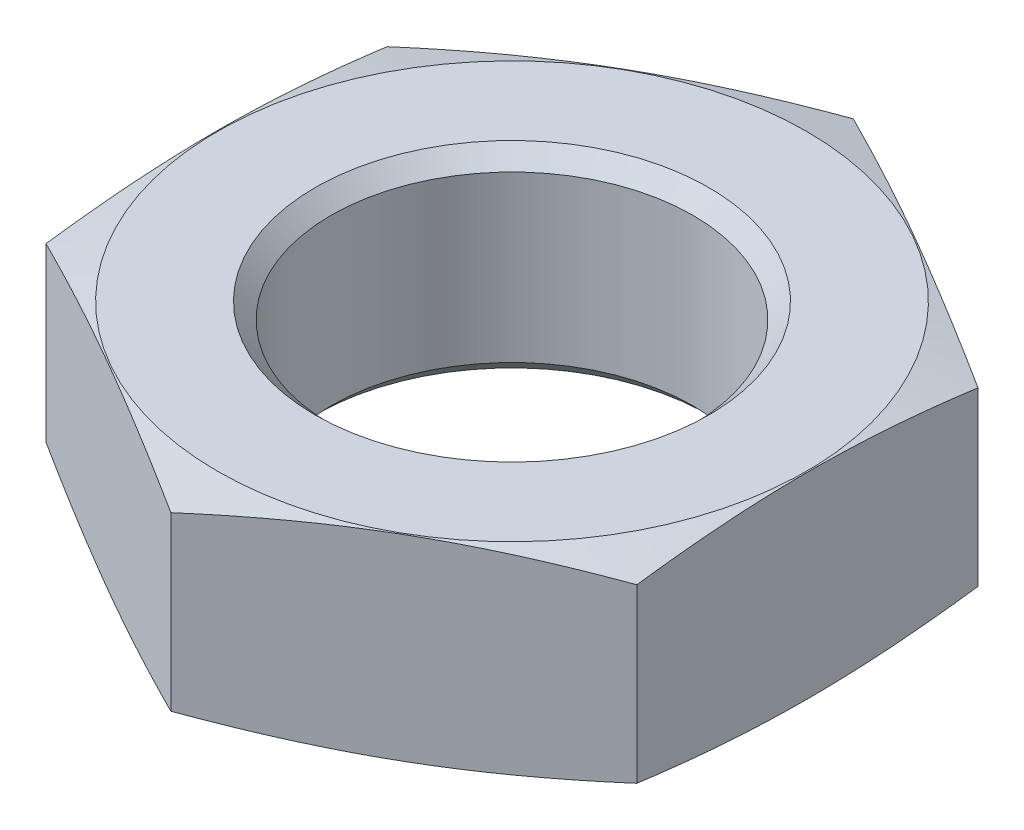
SolidWorks part; units mm, degrees
ref_plane "Front Plane" through (0, 0, 0) normal (0, 0, 1) x (1, 0, 0)
ref_plane "Top Plane" through (0, 0, 0) normal (0, 1, 0) x (1, 0, 0)
ref_plane "Right Plane" through (0, 0, 0) normal (1, 0, 0) x (0, 0, -1)
sketch "Sketch1" plane through (0, 0, 0) normal (0, 0, 1) x (1, 0, 0)
  line L0 (0, 0) -> (14.95, 0)
  line L1 (14.95, 0) -> (33.6103, -5)
  line L2 (33.6103, -5) -> (14.95, -10)
  line L3 (14.95, -10) -> (0, -10)
  line L4 (0, -10) -> (0, 0)
  line L5 (0, -10) -> (0, 0) construction
revolve "Revolve1" add sketch "Sketch1" angle 360 about L5
sketch "Sketch2" plane through (0, 0, 0) normal (0, 1, 0) x (1, 0, 0)
  line L0 (-60, 60) -> (-60, -60)
  line L1 (-60, -60) -> (60, -60)
  line L2 (60, -60) -> (60, 60)
  line L3 (60, 60) -> (-60, 60)
  line L4 (-15, -8.6603) -> (0, -17.3205)
  line L5 (0, -17.3205) -> (15, -8.6603)
  line L6 (15, -8.6603) -> (15, 8.6603)
  line L7 (15, 8.6603) -> (0, 17.3205)
  line L8 (0, 17.3205) -> (-15, 8.6603)
  line L9 (-15, 8.6603) -> (-15, -8.6603)
extrude "Cut-Extrude1" cut sketch "Sketch2" along normal blind 11 and the other way blind 11
sketch "Sketch3" plane through (0, 0, 0) normal (0, 0, 1) x (1, 0, 0)
  line L0 (0, 0) -> (10, 0)
  line L1 (10, 0) -> (9.188, -0.812)
  line L2 (9.188, -0.812) -> (9.188, -9.188)
  line L3 (9.188, -9.188) -> (10, -10)
  line L4 (10, -10) -> (0, -10)
  line L5 (0, -10) -> (0, 0)
  line L6 (0, -10) -> (0, 0) construction
revolve "Cut-Revolve1" cut sketch "Sketch3" angle 360 about L6 reverse direction yes
cosmetic thread "Cosmetic Thread1" parameters "D1"=10, "D2"=20
ref_plane "Plane1" through (0, -5, 0) normal (0, 1, 0) x (1, 0, 0)
ref_plane "2CYL XY" through (0, -5, 0) normal (0, 1, 0) x (1, 0, 0)
ref_plane "2CYL XZ" through (0, 0, 0) normal (0, 0, 1) x (1, 0, 0)
ref_plane "2CYL YZ" through (0, 0, 0) normal (1, 0, 0) x (0, 0, -1)
ref_axis "2CYL X" through (-80.9, -5, 0) along (1, 0, 0)
ref_axis "2CYL Y" through (0, -5, 50) along (0, 0, -1)
ref_axis "2CYL Z" through (0, 50, 0) along (0, -1, 0)
sketch3d "2CYL"
  point P0 (0, -5, 0)
ref_plane "din439b_punkt XY" through (0, 0, 0) normal (0, 1, 0) x (1, 0, 0)
ref_plane "din439b_punkt XZ" through (0, 0, 0) normal (0, 0, 1) x (1, 0, 0)
ref_plane "din439b_punkt YZ" through (0, 0, 0) normal (1, 0, 0) x (0, 0, -1)
ref_axis "din439b_punkt X" through (-80.9, 0, 0) along (1, 0, 0)
ref_axis "din439b_punkt Y" through (0, 0, 50) along (0, 0, -1)
ref_axis "din439b_punkt Z" through (0, 50, 0) along (0, -1, 0)
sketch3d "din439b_punkt"
  point P0 (0, 0, 0)
other "Freeze***"
